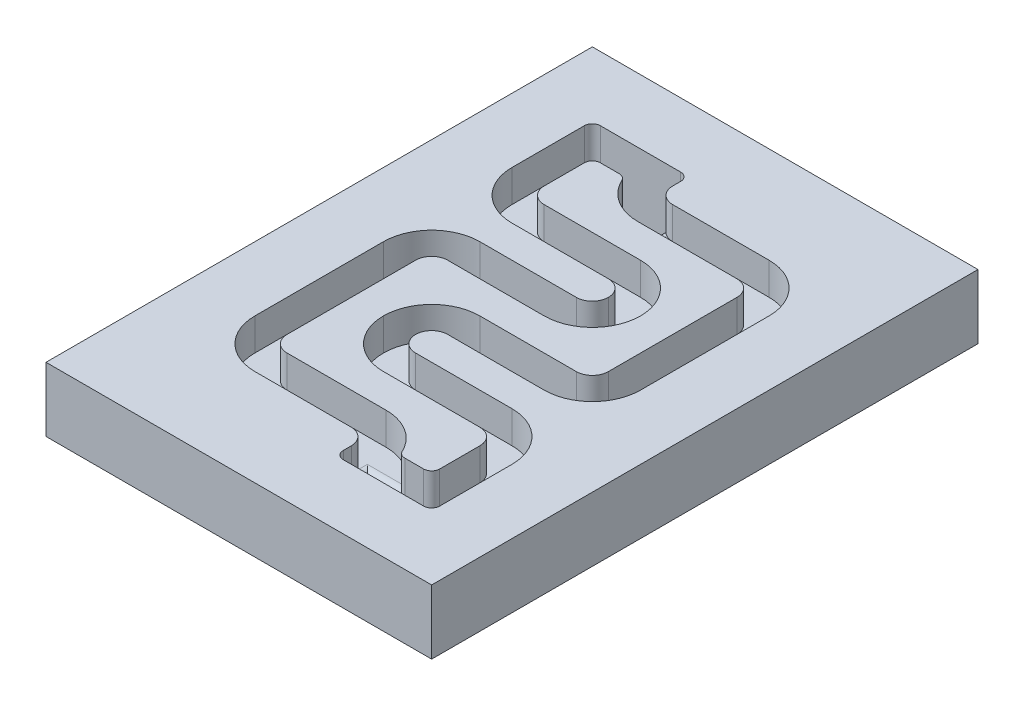
SolidWorks part; units mm, degrees
ref_plane "Ebene vorne" through (0, 0, 0) normal (0, 0, 1) x (1, 0, 0)
ref_plane "Ebene oben" through (0, 0, 0) normal (0, 1, 0) x (1, 0, 0)
ref_plane "Ebene rechts" through (0, 0, 0) normal (1, 0, 0) x (0, 0, -1)
sketch "Skizze1" plane through (0, 0, 0) normal (0, 1, 0) x (1, 0, 0)
  line L1 (0, 0) -> (12, 0)
  line L2 (0, 0) -> (0, 17)
  line L3 (0, 17) -> (12, 17)
  line L4 (12, 0) -> (12, 17)
  dimension "D1" = 17
  dimension "D2" = 12
extrude "Aufsatz-Linear austragen1" add sketch "Skizze1" along normal blind 2
sketch "Skizze2" plane through (0, 2, 0) normal (0, 1, 0) x (1, 0, 0)
  line L0 (0, 17) -> (0, 0) construction
  line L1 (10, 15) -> (2, 15)
  line L2 (10, 15) -> (10, 2)
  line L3 (10, 2) -> (2, 2)
  line L4 (2, 15) -> (2, 2)
  line L5 (0, 0) -> (12, 0) construction
  dimension "D1" = 13
  dimension "D2" = 8
  dimension "D3" = 2
  dimension "D4" = 2
sketch "Skizze4" plane through (0, 2, 0) normal (0, 1, 0) x (1, 0, 0)
  line L1 (10, 3) -> (7, 3)
  line L2 (10, 3) -> (10, 2)
  line L3 (10, 2) -> (7, 2)
  line L4 (7, 3) -> (7, 2)
  line L5 (2, 14) -> (5, 14)
  line L6 (2, 14) -> (2, 15)
  line L7 (2, 15) -> (5, 15)
  line L8 (5, 14) -> (5, 15)
  dimension "D1" = 1
  dimension "D2" = 3
  dimension "D3" = 3
  dimension "D4" = 1
sketch "Skizze3" plane through (0, 2, 0) normal (0, 1, 0) x (1, 0, 0)
  line L0 (2, 14) -> (2, 11)
  line L1 (2, 14) -> (3, 14)
  line L3 (3, 14) -> (3, 12)
  line L4 (3, 12) -> (8, 12)
  line L5 (4, 14) -> (4, 13)
  line L6 (4, 13) -> (9, 13)
  line L7 (8, 12) -> (8, 9)
  line L8 (8, 9) -> (3, 9)
  line L9 (2, 11) -> (7, 11)
  line L10 (7, 11) -> (7, 10)
  line L11 (7, 10) -> (2, 10)
  line L14 (4, 14) -> (10, 14)
  line L15 (10, 14) -> (10, 7)
  line L16 (9, 13) -> (9, 8)
  line L17 (9, 8) -> (4, 8)
  line L18 (4, 8) -> (4, 5)
  line L19 (10, 7) -> (5, 7)
  line L25 (5, 7) -> (5, 6)
  line L26 (5, 6) -> (10, 6)
  line L27 (10, 6) -> (10, 3)
  line L28 (10, 3) -> (9, 3)
  line L29 (9, 3) -> (9, 5)
  line L30 (9, 5) -> (4, 5)
  line L31 (2, 10) -> (2, 3)
  line L32 (2, 3) -> (8, 3)
  line L33 (8, 3) -> (8, 4)
  line L34 (8, 4) -> (3, 4)
  line L35 (3, 4) -> (3, 9)
  dimension "D1" = 1
  dimension "D2" = 1
  dimension "D3" = 1
  dimension "D4" = 1
  dimension "D5" = 3
  dimension "D6" = 7
  dimension "D7" = 1
  dimension "D8" = 7
  dimension "D9" = 3
  dimension "D10" = 1
  dimension "D11" = 1
  dimension "D12" = 6
  dimension "D13" = 1
  dimension "D14" = 1
  dimension "D15" = 1
  dimension "D16" = 1
  dimension "D17" = 6
  dimension "D18" = 6
  dimension "D19" = 6
  dimension "D20" = 1
  dimension "D21" = 1
  dimension "D22" = 1
  dimension "D23" = 6
  dimension "D24" = 6
  dimension "D25" = 1
  dimension "D26" = 8
extrude "Schnitt-Linear austragen1" cut sketch "Skizze4" against normal through all and the other way through all contours L1 L4 L3 L2 | L8 L7 L6 L5 region at (8.5, 2, -2.5)
extrude "Schnitt-Linear austragen3" cut sketch "Skizze3" against normal blind 1 contours L34 L35 L8 L7 L4 L3 L1 L0 L9 L10 L11 L31 L32 L33 | L30 L29 L28 L27 L26 L25 L19 L15 L14 L5 L6 L16 L17 L18 region at (2.5, 2, -13.8747) region at (7, 2, -13.8747)
fillet "Verrundung1" radius 0.5 12 edges at (3, 1.5, -12) (3, 1.5, -9) (3, 1.5, -4) (5, 1.5, -6) (5, 1.5, -7) (9, 1.5, -13) (7, 1.5, -10) (7, 1.5, -11) (9, 1.5, -8) (9, 1.5, -5) (5, 1.5, -14) (7, 1.5, -3)
fillet "Verrundung2" radius 1.5 12 edges at (4, 1.5, -8) (8, 1.5, -4) (4, 1.5, -13) (10, 1.5, -14) (2, 1.5, -11) (10, 1.5, -7) (10, 1.5, -6) (2, 1.5, -3) (2, 1.5, -10) (8, 1.5, -12) (8, 1.5, -9) (4, 1.5, -5)
fillet "Verrundung3" radius 0.25 14 edges at (9.5, 1, -3) (7.5, 1, -3) (7, 1, -2.75) (5, 1, -14.25) (4.5, 1, -14) (2.5, 1, -14) (4, 1.5, -14) (3, 1.5, -14) (2, 1, -15) (5, 1, -15) (9, 1.5, -3) (8, 1.5, -3) (10, 1, -2) (7, 1, -2)
